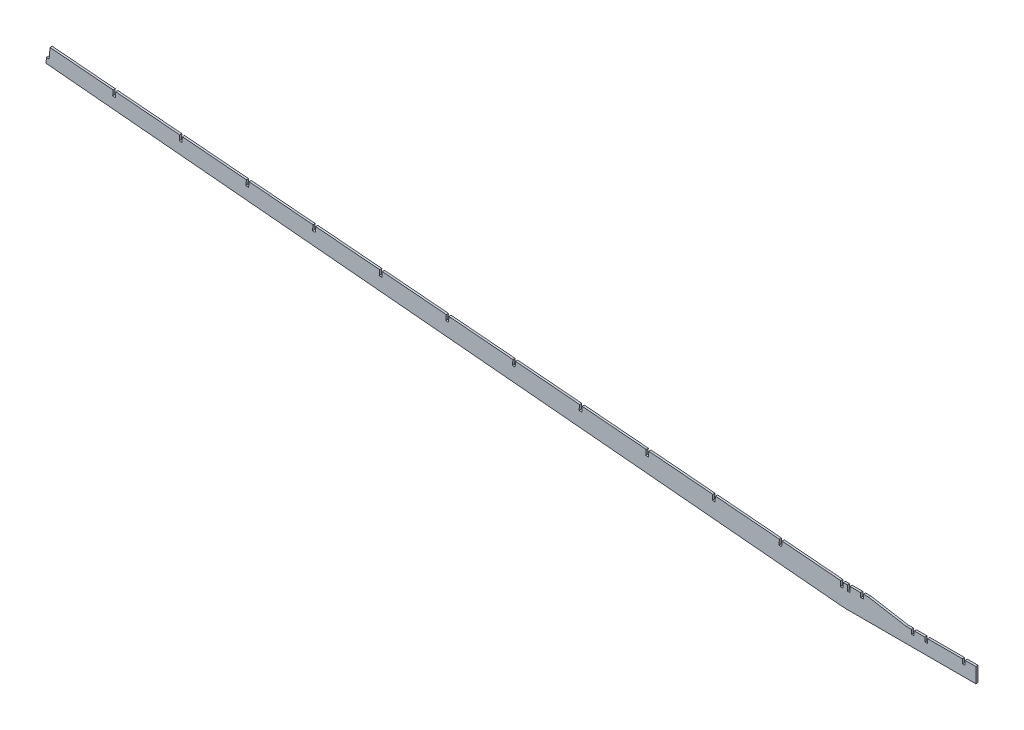
SolidWorks part; units mm, degrees
ref_plane "Front Plane" through (0, 0, 0) normal (0, 0, 1) x (1, 0, 0)
ref_plane "Top Plane" through (0, 0, 0) normal (0, 1, 0) x (1, 0, 0)
ref_plane "Right Plane" through (0, 0, 0) normal (1, 0, 0) x (0, 0, -1)
sketch "Sketch1" plane through (0, 0, 0) normal (0, 0, 1) x (1, 0, 0)
  line L0 (-949.6524, 80.0757) -> (-9.8872, -5.2596)
  line L1 (-945.9572, 86.1378) -> (-949.6524, 80.0757)
  line L8 (-6.7234, -5.5253) -> (-5.1293, 13.4579)
  line L9 (-5.1293, 13.4579) -> (-8.2932, 13.7235)
  line L10 (-8.2932, 13.7235) -> (-9.8872, -5.2596)
  line L11 (-9.8872, -5.2596) -> (-6.7234, -5.5253)
  line L12 (3.175, -5.8337) -> (3.175, 13.2163)
  line L13 (3.175, 13.2163) -> (0, 13.2163)
  line L14 (0, 13.2163) -> (0, -5.8337)
  line L15 (0, -5.8337) -> (3.175, -5.8337)
  line L17 (-943.1142, 119.9943) -> (-945.9572, 86.1378)
  line L18 (-945.9572, 86.1378) -> (-9.8872, -5.2596)
  line L19 (-6.7234, -5.5253) -> (0, -5.8337)
  line L20 (3.175, -5.8337) -> (152.4, -5.8337)
  line L21 (152.4, -5.8337) -> (152.4, 11.9463)
  line L22 (152.4, 11.9463) -> (69.85, 11.9463)
  line L23 (69.85, 11.9463) -> (25.4, 19.5663)
  line L24 (25.4, 19.5663) -> (-1.9861, 19.5663)
  line L25 (-1.9861, 19.5663) -> (-944.8986, 98.7448)
  line L26 (0, 13.2163) -> (0, 19.5663)
  line L27 (3.175, 13.2163) -> (3.175, 19.5663)
  line L28 (-5.1293, 13.4579) -> (-4.598, 19.7856)
  line L29 (-8.2932, 13.7235) -> (-7.7618, 20.0513)
  line L30 (-8.2932, 13.7235) -> (-945.4292, 92.426)
  line L31 (15.875, 19.5663) -> (15.875, 14.4863)
  line L32 (15.875, 14.4863) -> (19.05, 14.4863)
  line L33 (19.05, 14.4863) -> (19.05, 19.5663)
  line L34 (76.2, 6.8663) -> (76.2, 11.9463)
  line L35 (76.2, 6.8663) -> (79.375, 6.8663)
  line L36 (79.375, 6.8663) -> (79.375, 11.9463)
  line L37 (92.075, 11.9463) -> (92.075, 6.8663)
  line L38 (92.075, 6.8663) -> (95.25, 6.8663)
  line L39 (95.25, 6.8663) -> (95.25, 11.9463)
  line L40 (136.525, 11.9463) -> (136.525, 6.8663)
  line L41 (136.525, 6.8663) -> (139.7, 6.8663)
  line L42 (139.7, 6.8663) -> (139.7, 11.9463)
  line L44 (-949.6524, 80.0757) -> (-949.1211, 86.4035)
  line L45 (-949.1211, 86.4035) -> (-945.959, 86.1163)
  dimension "D1" = 25.4
  dimension "D2" = 6.35
extrude "Boss-Extrude1" add sketch "Sketch1" along normal blind 2.54 contours L42 L41 L40 L22 L39 L38 L37 L36 L35 L34 L23 L24 L33 L32 L31 L27 L12 L20 L21 | L30 L29 L25 L17 | L28 L8 L19 L14 L26 L24 L25 | L10 L11 L8 L9 | L14 L15 L12 L13 | L45 L44 L17 | L10 L30 L17 L18 | L18 L1 L0 region at (-635.1656, 53.6513, 0) region at (-948.2478, 84.1988, 0) region at (-398.9758, 39.6362, 0) region at (-7.5083, 4.0991, 0) region at (-476.4854, 56.2272, 0) region at (-2.8648, 6.1846, 0) region at (1.5875, 3.6913, 0) region at (71.853, 4.2703, 0)
sketch "Sketch2" plane through (0, 0, 2.54) normal (0, 0, 1) x (1, 0, 0)
  line L1 (-76.483, 72.8473) -> (-82.5095, 1.0799)
  line L3 (-155.6446, 77.1971) -> (-161.4339, 8.255)
  line L5 (-234.8005, 81.6162) -> (-240.3617, 15.3891)
  line L7 (-313.9625, 85.9617) -> (-319.2865, 22.5591)
  line L9 (-393.1191, 90.3714) -> (-398.2146, 29.6908)
  line L11 (-472.2837, 94.686) -> (-477.1388, 36.8682)
  line L13 (-551.4418, 99.0783) -> (-556.0668, 44.0001)
  line L15 (-630.6082, 103.3716) -> (-634.991, 51.1773)
  line L17 (-709.7674, 107.7507) -> (-713.9195, 58.3043)
  line L19 (-788.9364, 112.0121) -> (-792.8436, 65.483)
  line L21 (-868.0976, 116.3681) -> (-871.7723, 72.6069)
  line L23 (-73.3191, 72.5816) -> (-79.3456, 0.8143)
  line L25 (-152.4808, 76.9314) -> (-158.27, 7.9893)
  line L27 (-231.6366, 81.3506) -> (-237.1978, 15.1234)
  line L29 (-310.7986, 85.696) -> (-316.1227, 22.2934)
  line L31 (-389.9552, 90.1057) -> (-395.0507, 29.4251)
  line L33 (-469.1198, 94.4203) -> (-473.9749, 36.6025)
  line L35 (-548.2779, 98.8126) -> (-552.903, 43.7344)
  line L37 (-627.4443, 103.1059) -> (-631.8272, 50.9116)
  line L39 (-706.6035, 107.485) -> (-710.7556, 58.0386)
  line L41 (-785.7726, 111.7464) -> (-789.6797, 65.2173)
  line L43 (-864.9337, 116.1024) -> (-868.6084, 72.3413)
  line L45 (-8.2932, 13.7235) -> (-945.4292, 92.426)
  line L47 (-7.7618, 20.0513) -> (-944.8986, 98.7448)
  line M27 (-7.7618, 20.0513) -> (-944.8986, 98.7448)
extrude "Cut-Extrude1" cut sketch "Sketch2" against normal through all and the other way through all contours L45 L43 L21 M27 | L45 L41 L19 M27 | L45 L39 L17 M27 | L45 L37 L15 M27 | L45 L35 L13 M27 | L45 L33 L11 M27 | L45 L31 L9 M27 | L45 L29 L7 M27 | L45 L27 L5 M27 | L45 L25 L3 M27 | L45 L23 L1 M27 region at (-79.0879, 22.8549, 2.54) region at (-158.0579, 29.4865, 2.54) region at (-237.0279, 36.1182, 2.54) region at (-315.998, 42.7499, 2.54) region at (-394.968, 49.3816, 2.54) region at (-473.938, 56.0132, 2.54) region at (-552.9081, 62.6449, 2.54) region at (-631.8781, 69.2766, 2.54) region at (-710.8481, 75.9083, 2.54) region at (-789.8182, 82.54, 2.54) region at (-868.7882, 89.1716, 2.54)
